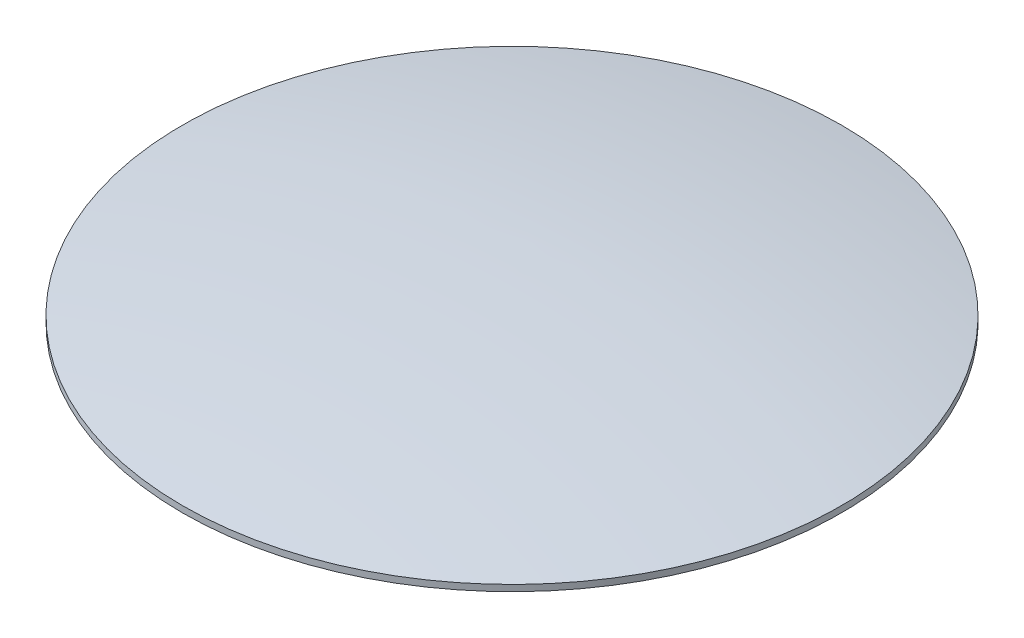
SolidWorks part; units mm, degrees
ref_plane "Front Plane" through (0, 0, 0) normal (0, 0, 1) x (1, 0, 0)
ref_plane "Top Plane" through (0, 0, 0) normal (0, 1, 0) x (1, 0, 0)
ref_plane "Right Plane" through (0, 0, 0) normal (1, 0, 0) x (0, 0, -1)
sketch "Sketch1" plane through (0, 0, 0) normal (0, 1, 0) x (1, 0, 0)
  circle A0 centre (0, 0) radius 13.335
  dimension "D1" = 26.67
extrude "Extrude1" add sketch "Sketch1" along normal blind 0.254
dome "Dome1" faces to dome 1 distance 1.27 reverse direction no elliptical dome no face at (0, 0.254, 13.335) parameters "D1"=1.27
